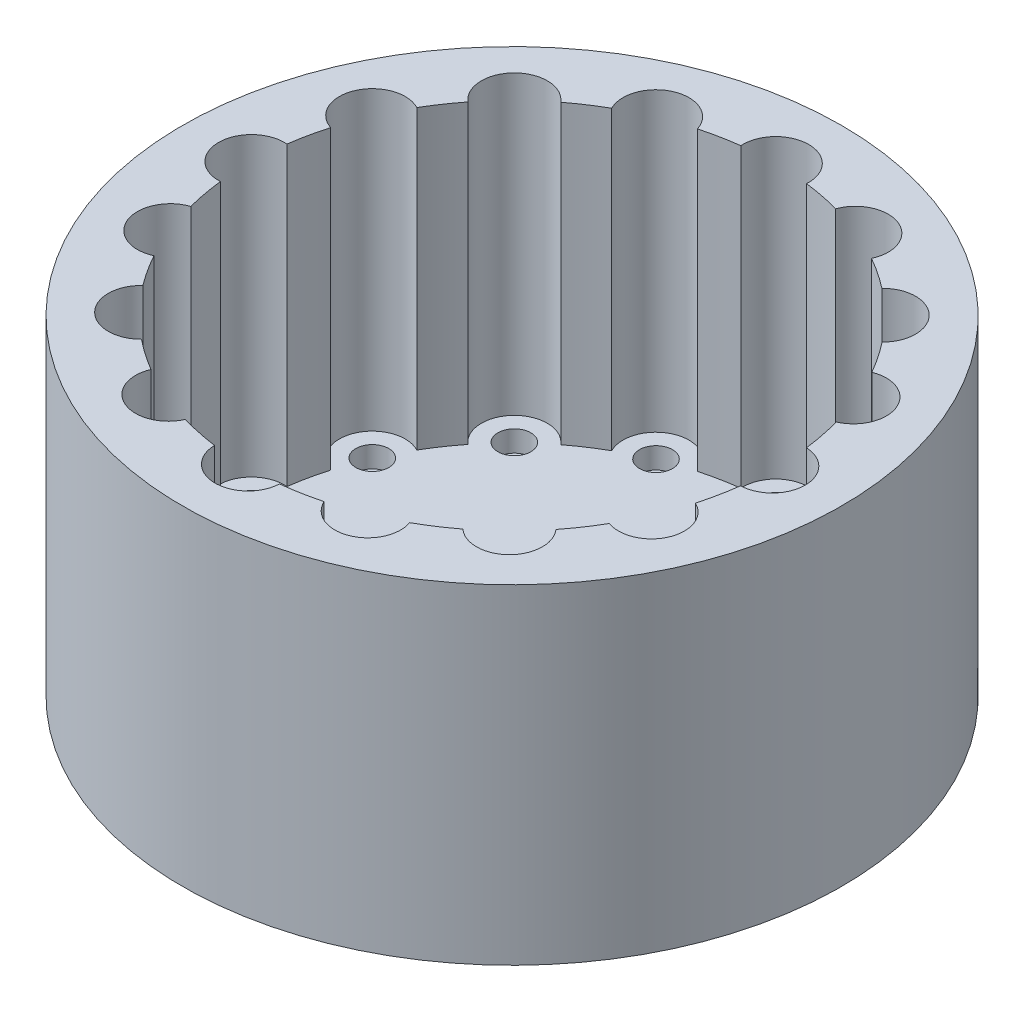
SolidWorks part; units mm, degrees
ref_plane "Front Plane" through (0, 0, 0) normal (0, 0, 1) x (1, 0, 0)
ref_plane "Top Plane" through (0, 0, 0) normal (0, 1, 0) x (1, 0, 0)
ref_plane "Right Plane" through (0, 0, 0) normal (1, 0, 0) x (0, 0, -1)
sketch "Sketch1" plane through (0, 0, 0) normal (0, 1, 0) x (1, 0, 0)
  arc A0 (-38.4721, 10.9498) -> (-39.6225, 5.4827) centre (0, 0) ccw
  arc A1 (4.9902, 39.6875) -> (-4.9902, 39.6875) centre (0, 40) ccw
  arc A2 (19.7423, 34.7885) -> (10.5038, 38.5963) centre (15.1971, 36.8722) ccw
  arc A3 (31.5425, 24.5981) -> (24.4561, 31.6528) centre (28.0405, 28.1668) ccw
  arc A4 (38.5639, 10.6218) -> (34.7247, 19.8543) centre (36.5748, 15.2091) ccw
  arc A5 (39.6831, -5.0248) -> (39.6903, 4.9683) centre (39.5008, -0.0281) ccw
  arc A6 (34.6812, -19.9303) -> (38.5373, -10.718) centre (36.373, -15.2253) ccw
  arc A7 (24.305, -31.769) -> (31.416, -24.7596) centre (27.6676, -28.0686) ccw
  arc A8 (10.1649, -38.6869) -> (19.4331, -34.9622) centre (14.7099, -36.6029) ccw
  arc A9 (-5.5266, -39.6164) -> (4.4678, -39.7497) centre (-0.5273, -39.5289) ccw
  arc A10 (-20.3279, -34.4496) -> (-11.148, -38.4151) centre (-15.7245, -36.4011) ccw
  arc A11 (-31.9737, -24.0351) -> (-25.0145, -31.2134) centre (-28.5678, -27.6957) ccw
  arc A12 (-38.7274, -10.0096) -> (-35.0397, -19.2929) centre (-37.1021, -14.7381) ccw
  arc A13 (-39.6225, 5.4827) -> (-39.7469, -4.4929) centre (-40.0281, 0.4992) ccw
  arc A14 (-34.5711, 20.1207) -> (-38.4721, 10.9498) centre (-36.9003, 15.6963) ccw
  arc A15 (-24.3492, 31.7351) -> (-31.4368, 24.7331) centre (-28.1949, 28.5397) ccw
  arc A16 (-10.477, 38.6035) -> (-19.6974, 34.814) centre (-15.2373, 37.074) ccw
  circle A17 centre (0, 0) radius 50
  arc A18 (-31.4368, 24.7331) -> (-34.5711, 20.1207) centre (0, 0) ccw
  arc A19 (-19.6974, 34.814) -> (-24.3492, 31.7351) centre (0, 0) ccw
  arc A20 (-4.9902, 39.6875) -> (-10.477, 38.6035) centre (0, 0) ccw
  arc A21 (10.5038, 38.5963) -> (4.9902, 39.6875) centre (0, 0) ccw
  arc A22 (24.4561, 31.6528) -> (19.7423, 34.7885) centre (0, 0) ccw
  arc A23 (34.7247, 19.8543) -> (31.5425, 24.5981) centre (0, 0) ccw
  arc A24 (39.6903, 4.9683) -> (38.5639, 10.6218) centre (0, 0) ccw
  arc A25 (38.5373, -10.718) -> (39.6831, -5.0248) centre (0, 0) ccw
  arc A26 (31.416, -24.7596) -> (34.6812, -19.9303) centre (0, 0) ccw
  arc A27 (19.4331, -34.9622) -> (24.305, -31.769) centre (0, 0) ccw
  arc A28 (-11.148, -38.4151) -> (-5.5266, -39.6164) centre (0, 0) ccw
  arc A29 (-25.0145, -31.2134) -> (-20.3279, -34.4496) centre (0, 0) ccw
  arc A30 (-35.0397, -19.2929) -> (-31.9737, -24.0351) centre (0, 0) ccw
  arc A31 (-39.7469, -4.4929) -> (-38.7274, -10.0096) centre (0, 0) ccw
  arc A32 (4.4678, -39.7497) -> (10.1649, -38.6869) centre (0, 0) ccw
  point P38 (-0.2637, 0.2355)
  dimension "D1" = 16
  dimension "D2" = 100
  dimension "D3" = 5
extrude "Boss-Extrude1" add sketch "Sketch1" along normal blind 45
sketch "Sketch2" plane through (0, 0, 0) normal (0, -1, 0) x (1, 0, 0)
  circle A0 centre (0, 0) radius 50
extrude "Boss-Extrude2" add sketch "Sketch2" along normal blind 5
sketch "Sketch4" plane through (0, 0, 0) normal (0, 1, 0) x (1, 0, 0)
  circle A0 centre (0, 0) radius 17.5
  dimension "D1" = 35
extrude "Cut-Extrude2" cut sketch "Sketch4" against normal blind 10
sketch "Sketch5" plane through (0, 0, 0) normal (0, 1, 0) x (1, 0, 0)
  circle A0 centre (-28.1949, 28.5397) radius 2.5
  circle A1 centre (-15.2373, 37.074) radius 2.5
  circle A2 centre (0, 40) radius 2.5
  circle A3 centre (15.1971, 36.8722) radius 2.5
  circle A4 centre (-36.9003, 15.6963) radius 2.5
  circle A5 centre (-40.0281, 0.4992) radius 2.5
  circle A6 centre (-37.1021, -14.7381) radius 2.5
  circle A7 centre (-28.5678, -27.6957) radius 2.5
  circle A8 centre (-15.7245, -36.4011) radius 2.5
  circle A9 centre (-0.5273, -39.5289) radius 2.5
  circle A10 centre (14.7099, -36.6029) radius 2.5
  circle A11 centre (27.6676, -28.0686) radius 2.5
  circle A12 centre (36.373, -15.2253) radius 2.5
  circle A13 centre (39.5008, -0.0281) radius 2.5
  circle A14 centre (36.5748, 15.2091) radius 2.5
  circle A15 centre (28.0405, 28.1668) radius 2.5
extrude "Cut-Extrude3" cut sketch "Sketch5" against normal blind 3.2
